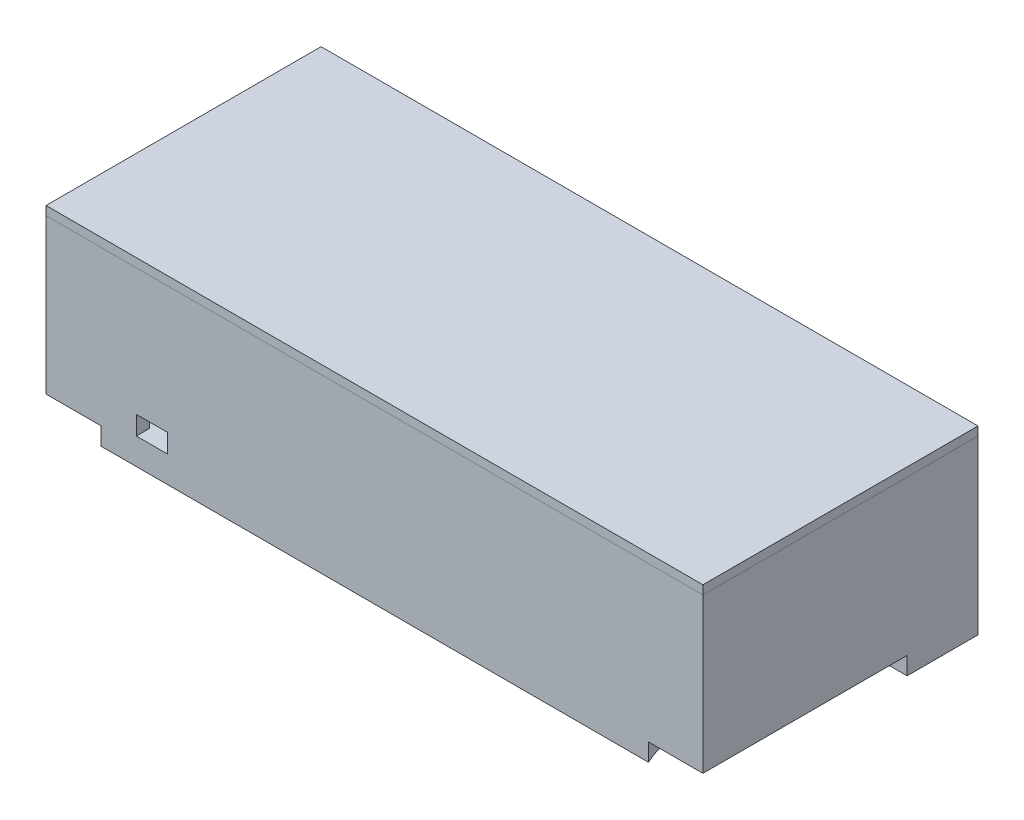
SolidWorks part; units mm, degrees
note: The reader was unsure of these and kept them because the rebuilt part matched: shared geometry of "Sketch1<3>", "Sketch8<3>".
ref_plane "Front Plane" through (0, 0, 0) normal (0, 0, 1) x (1, 0, 0)
ref_plane "Top Plane" through (0, 0, 0) normal (0, 1, 0) x (1, 0, 0)
ref_plane "Right Plane" through (0, 0, 0) normal (1, 0, 0) x (0, 0, -1)
sketch "Sketch1" plane through (0, 0, 0) normal (0, 1, 0) x (1, 0, 0)
  line L0 (35.6, 10.95) -> (35.6, -21.05)
  line L1 (33, -26.65) -> (-32, -26.65)
  line L2 (33, -26.65) -> (33, -23.65)
  line L3 (32, 26.65) -> (-32, 26.65)
  line L4 (-33, -25.65) -> (-33, 25.65)
  line L5 (33, -26.65) -> (-33, 26.65) construction
  line L6 (33, 26.65) -> (-33, -26.65) construction
  line L7 (35.6, -21.05) -> (33, -23.65)
  line L8 (35.6, 10.95) -> (33, 13.55)
  line L9 (33, 13.55) -> (33, 25.65)
  line L10 (-32, -26.65) -> (-33, -25.65)
  line L11 (-33, 25.65) -> (-32, 26.65)
  line L12 (33, 25.65) -> (32, 26.65)
  line L13 (-19, 24.15) -> (-19, -24.15) construction
  line L14 (-61, 21.5705) -> (-61, -21.8763)
  line L15 (-61, -21.8763) -> (-103.5118, -21.8763)
  line L16 (-103.5118, -21.8763) -> (-103.5118, 21.5705)
  line L17 (-103.5118, 21.5705) -> (-61, 21.5705)
  line L18 (-100.9051, -18.8263) -> (-100.9051, 18.5205)
  line L19 (-100.9051, 18.5205) -> (-63.6067, 18.5205)
  line L20 (-63.6067, 18.5205) -> (-63.6067, -18.8263)
  line L21 (-63.6067, -18.8263) -> (-100.9051, -18.8263)
  line L22 (-61, -0.1529) -> (-33, 0) construction
  line L23 (-82.2559, 21.5705) -> (-82.2559, 18.5205) construction
  line L24 (-63.6067, -0.1529) -> (-61, -0.1529) construction
  line L25 (-105.8452, 28.2263) -> (37.9828, 28.2263)
  line L27 (-105.8452, -28.0958) -> (37.9828, -28.0958)
  line L28 (37.9828, 28.2263) -> (37.9828, -28.0958)
  line L29 (-105.8452, 28.2263) -> (-105.8452, -28.0958)
  circle A0 centre (-17.6, 24.15) radius 1.4
  circle A1 centre (-19, -24.15) radius 1.4
  circle A2 centre (33.2, -19.05) radius 1.4
  circle A3 centre (33.2, 8.85) radius 1.4
  circle A4 centre (-100.9051, 18.5205) radius 1.4
  circle A5 centre (-63.6067, 18.5205) radius 1.4
  circle A6 centre (-100.9051, -18.8263) radius 1.4
  circle A7 centre (-63.6067, -18.8263) radius 1.4
  point P0 (0, 0)
  point P41 (-41, -0.0437)
  dimension "D7" = 2.8
  dimension "D18" = 2.8
  dimension "D1" = 66
  dimension "D2" = 53.3
  dimension "D3" = 68.6
  dimension "D4" = 32
  dimension "D5" = 45
  dimension "D6" = 3
  dimension "D8" = 2.5
  dimension "D9" = 27.9
  dimension "D10" = 5.1
  dimension "D11" = 50.8
  dimension "D12" = 14
  dimension "D16" = 2.5
  dimension "D17" = 42.5118
  dimension "D19" = 43.4468
  dimension "D20" = 2.6067
  dimension "D21" = 20
  dimension "D22" = 8
extrude "Boss-Extrude1" add sketch "Sketch1" along normal blind 2
extrude "Boss-Extrude2" add sketch "Sketch1<3>" along normal blind 6 contours L20 A5 L19 | L19 A4 L18 | L18 A4 L19 | L19 A5 L20 | L20 A7 L21 | L21 A7 L20 | L18 A6 L21 | L21 A6 L18 | A3 | A0 | A1 | A2
sketch "Sketch1<3>" plane through (0, 0, 0) normal (0, 1, 0) x (1, 0, 0) same geometry as "Sketch1"
fillet "Fillet1" radius 0.6 8 edges at (33.2, 6, 20.45) (33.2, 6, -7.45) (-17.6, 6, -22.75) (-19, 6, 25.55) (-100.9051, 6, -17.1205) (-63.6067, 6, -17.1205) (-63.6067, 6, 20.2263) (-100.9051, 6, 20.2263)
sketch "Sketch2" plane through (0, 0, 28.0958) normal (0, 0, 1) x (1, 0, 0)
  line L0 (-105.8452, 2) -> (-105.8452, 0) construction
  line L1 (-105.8452, 0) -> (37.9828, 0)
  line L2 (-105.8452, 0) -> (-105.8452, 35)
  line L3 (-105.8452, 35) -> (37.9828, 35)
  line L4 (37.9828, 0) -> (37.9828, 35)
  line L9 (-105.8452, 2) -> (37.9828, 2) construction
  line L10 (-88.375, 2) -> (-81.3266, 2)
  line L11 (-88.375, 2) -> (-88.375, 6.2491)
  line L12 (-88.375, 6.2491) -> (-81.3266, 6.2491)
  line L13 (-81.3266, 2) -> (-81.3266, 6.2491)
  line L14 (37.9828, 2) -> (37.9828, 0) construction
  dimension "D1" = 35
extrude "Boss-Extrude3" add sketch "Sketch2" along normal blind 3
sketch "Sketch3" plane through (0, 0, -28.2263) normal (0, 0, -1) x (-1, 0, 0)
  line L1 (-37.9828, 0) -> (105.8452, 0)
  line L2 (-37.9828, 0) -> (-37.9828, 35)
  line L3 (-37.9828, 35) -> (105.8452, 35)
  line L4 (105.8452, 0) -> (105.8452, 35)
  line L5 (39, 2) -> (52.5, 2)
  line L6 (39, 2) -> (39, 15)
  line L7 (39, 15) -> (52.5, 15)
  line L8 (52.5, 2) -> (52.5, 15)
  line L9 (105.8452, 35) -> (105.8452, 2) construction
  line L10 (81.3266, 2) -> (-37.9828, 2) construction
  line L14 (19, 2) -> (19, 5.4) construction
  point P5 (0, 0)
  point P10 (41.9932, 2)
  point P12 (0, 0)
  dimension "D1" = 13.5
  dimension "D2" = 13
  dimension "D3" = 20
extrude "Boss-Extrude4" add sketch "Sketch3" along normal blind 3
sketch "Sketch5" plane through (37.9828, 0, 0) normal (1, 0, 0) x (0, 0, -1)
  line L1 (-31.0958, 0) -> (31.2263, 0)
  line L2 (-31.0958, 0) -> (-31.0958, 35)
  line L3 (-31.0958, 35) -> (31.2263, 35)
  line L4 (31.2263, 0) -> (31.2263, 35)
extrude "Boss-Extrude7" add sketch "Sketch5" along normal blind 2
sketch "Sketch7" plane through (0, 0, 0) normal (0, -1, 0) x (-1, 0, 0)
  line L0 (122.0606, -31.4178) -> (-39.9828, 31.2263) construction
  line L1 (-39.9828, -31.0958) -> (-39.9828, 31.2263) construction
  line L2 (122.0606, -15.3457) -> (-39.9828, -15.3457)
  line L3 (122.0606, -15.3457) -> (122.0606, 15.1543)
  line L4 (122.0606, 15.1543) -> (-39.9828, 15.1543)
  line L5 (-39.9828, -15.3457) -> (-39.9828, 15.1543)
  line L6 (122.0606, -15.3457) -> (-39.9828, 15.1543) construction
  line L7 (122.0606, 15.1543) -> (-39.9828, -15.3457) construction
  line L9 (122.0606, -31.4178) -> (-39.9828, -31.4178)
  line L10 (122.0606, -31.4178) -> (122.0606, 31.2263)
  line L11 (122.0606, 31.2263) -> (-39.9828, 31.2263)
  line L12 (-39.9828, -31.4178) -> (-39.9828, 31.2263)
  line L13 (122.0606, -31.4178) -> (-39.9828, 31.2263) construction
  line L14 (122.0606, 31.2263) -> (-39.9828, -31.4178) construction
  point P4 (41.0389, -0.0957)
  point P11 (41.0389, -0.0957)
  dimension "D1" = 30.5
extrude "Boss-Extrude8" add sketch "Sketch7" along normal blind 4
sketch "Sketch8" plane through (0, 0, -31.2263) normal (0, 0, -1) x (-1, 0, 0)
  line L0 (45.75, 15) -> (45.75, 2) construction
  line L1 (52.5, 15) -> (39, 15) construction
  line L2 (39, 2) -> (52.5, 2) construction
  line L3 (105.8452, -4) -> (-39.9828, -4) construction
  line L4 (105.8452, -4) -> (-39.9828, -4) construction
  line L5 (39, 2) -> (52.5, 2)
  line L6 (39, 2) -> (39, 15)
  line L7 (39, 15) -> (52.5, 15)
  line L8 (52.5, 2) -> (52.5, 15)
  line L10 (24, 17) -> (9, 17)
  line L11 (24, 17) -> (24, 25.5)
  line L12 (24, 25.5) -> (9, 25.5)
  line L13 (9, 17) -> (9, 25.5)
  circle A0 centre (45.75, 8.5) radius 5
  circle A1 centre (72.5, 24) radius 3.5
  point P23 (0, 0)
  point P24 (0, 0)
  point P25 (0, 0)
  point P26 (0, 0)
  point P27 (0, 0)
  point P28 (0, 0)
  line M9 (39, 2) -> (39, 15)
  line M10 (39, 15) -> (52.5, 15)
  line M11 (52.5, 15) -> (52.5, 2)
  line M12 (52.5, 2) -> (39, 2)
  dimension "D1" = 10
  dimension "D3" = 7
  dimension "D2" = 20
  dimension "D4" = 15
  dimension "D5" = 15
  dimension "D6" = 8.5
  dimension "D7" = 21
  dimension "D8" = 28
extrude "Boss-Extrude13" add sketch "Sketch8" against normal blind 3 contours A0 M9 M12 M11 M10 | L0 L5 A0 M10 M9
extrude "Cut-Extrude1" cut sketch "Sketch8<3>" against normal blind 3 contours L13 L10 L11 L12 | A1
sketch "Sketch8<3>" plane through (0, 0, -31.2263) normal (0, 0, -1) x (-1, 0, 0) same geometry as "Sketch8"
sketch "Sketch9" plane through (-105.8452, 0, 0) normal (-1, 0, 0) x (0, 0, 1)
  line L0 (-28.2263, 35) -> (28.0958, 35)
  line L12 (-31.2263, 35) -> (-31.2263, -4)
  line L13 (-31.2263, -4) -> (-15.1543, -4)
  line L14 (-15.1543, -4) -> (-15.1543, 0)
  line L15 (-15.1543, 0) -> (15.3457, 0)
  line L16 (15.3457, 0) -> (15.3457, -4)
  line L17 (15.3457, -4) -> (31.0958, -4)
  line L18 (31.0958, -4) -> (31.0958, 35)
  line L19 (31.0958, 35) -> (28.0958, 35)
  line L20 (28.0958, 35) -> (28.0958, 2)
  line L21 (28.0958, 2) -> (-28.2263, 2)
  line L22 (-28.2263, 2) -> (-28.2263, 35)
  line L23 (-28.2263, 35) -> (-31.2263, 35)
  line L24 (-31.2263, 35) -> (-31.2263, -4)
  line L25 (-31.2263, -4) -> (-15.1543, -4)
  line L26 (-15.1543, -4) -> (-15.1543, 0)
  line L27 (-15.1543, 0) -> (15.3457, 0)
  line L28 (15.3457, 0) -> (15.3457, -4)
  line L29 (15.3457, -4) -> (31.0958, -4)
  line L30 (31.0958, -4) -> (31.0958, 35)
  line L31 (31.0958, 35) -> (28.0958, 35)
  line L35 (-28.2263, 35) -> (-31.2263, 35)
  dimension "D1" = 0
extrude "Boss-Extrude14" add sketch "Sketch9" along normal blind 3
sketch "Sketch10" plane through (0, 35, 0) normal (0, 1, 0) x (1, 0, 0)
  line L0 (-105.8452, 28.2263) -> (-105.8452, -28.0958) construction
  line L1 (-105.8452, 28.2263) -> (38.2182, 28.2263) construction
  line L2 (-105.8452, -28.0958) -> (38.2182, -28.0958) construction
  line L3 (38.2182, 28.2263) -> (38.2182, -28.0958) construction
  line L4 (-105.6952, 28.0763) -> (38.0682, 28.0763)
  line L5 (38.0682, 28.0763) -> (38.0682, -27.9458)
  line L6 (-105.6952, -27.9458) -> (38.0682, -27.9458)
  line L7 (-105.6952, 28.0763) -> (-105.6952, -27.9458)
  line L8 (-104.4952, 26.8763) -> (-104.4952, -26.7458)
  line L9 (-104.4952, -26.7458) -> (36.8682, -26.7458)
  line L10 (36.8682, 26.8763) -> (36.8682, -26.7458)
  line L11 (-104.4952, 26.8763) -> (36.8682, 26.8763)
  dimension "D1" = 0.15
  dimension "D2" = 1.2
extrude "Boss-Extrude15" add sketch "Sketch10" against normal blind 6 separate body
sketch "Sketch11" plane through (0, 35, 0) normal (0, 1, 0) x (1, 0, 0)
  line L0 (-104.4952, 26.8763) -> (36.8682, -26.7458) construction
  line L5 (-108.8452, 31.2263) -> (-108.8452, -31.0958)
  line L6 (-108.8452, -31.0958) -> (39.9828, -31.0958)
  line L7 (39.9828, -31.0958) -> (39.9828, 31.2263)
  line L8 (39.9828, 31.2263) -> (-108.8452, 31.2263)
  line L9 (-108.8452, 31.2263) -> (-108.8452, -31.0958)
  line L10 (-108.8452, -31.0958) -> (39.9828, -31.0958)
  line L11 (39.9828, -31.0958) -> (39.9828, 31.2263)
  line L12 (39.9828, 31.2263) -> (-108.8452, 31.2263)
  dimension "D1" = 0
extrude "Boss-Extrude16" add sketch "Sketch11" along normal blind 2
chamfer "Chamfer1" distance 2 angle 45 4 edges at (-104.4952, 35, -0.0653) (-33.8135, 35, 26.7458) (36.8682, 35, -0.0653) (-33.8135, 35, -26.8763)
sketch "Sketch12" plane through (0, -4, 0) normal (0, -1, 0) x (-1, 0, 0)
  line L1 (108.8452, 31.2263) -> (-39.9828, 31.2263) construction
  line L2 (34.4312, 31.2263) -> (34.4312, 130.9428) construction
sketch "Sketch13" plane through (0, -4, 0) normal (0, -1, 0) x (-1, 0, 0)
  line L11 (-39.9828, -0.0957) -> (108.8452, -0.0957) construction
  line L12 (-39.9828, -15.3457) -> (-39.9828, 15.1543) construction
  line L13 (108.8452, 15.1543) -> (108.8452, -15.3457) construction
  line L14 (-44.7783, -7.5234) -> (-49.5688, -45.0457)
  line L15 (112.2573, -6.4767) -> (-44.7783, -7.5234)
  line L16 (117.9312, -45.0457) -> (112.2573, -6.4767)
  line L17 (-25.3688, -14.8457) -> (94.2312, -13.3828)
  line L18 (-25.3688, -20.8457) -> (-25.3688, -14.8457)
  line L19 (94.2312, -21.3457) -> (94.2312, -13.3828)
  arc A10 (-25.3688, -20.8457) -> (-49.5688, -45.0457) centre (-49.5688, -20.8457) cw
  arc A13 (117.9312, -45.0457) -> (94.2312, -21.3457) centre (117.9312, -21.3457) cw
extrude "Cut-Extrude2" cut sketch "Sketch13" against normal up to surface (4 mm away) up to face at (-34.4312, 0, 0.0957)
